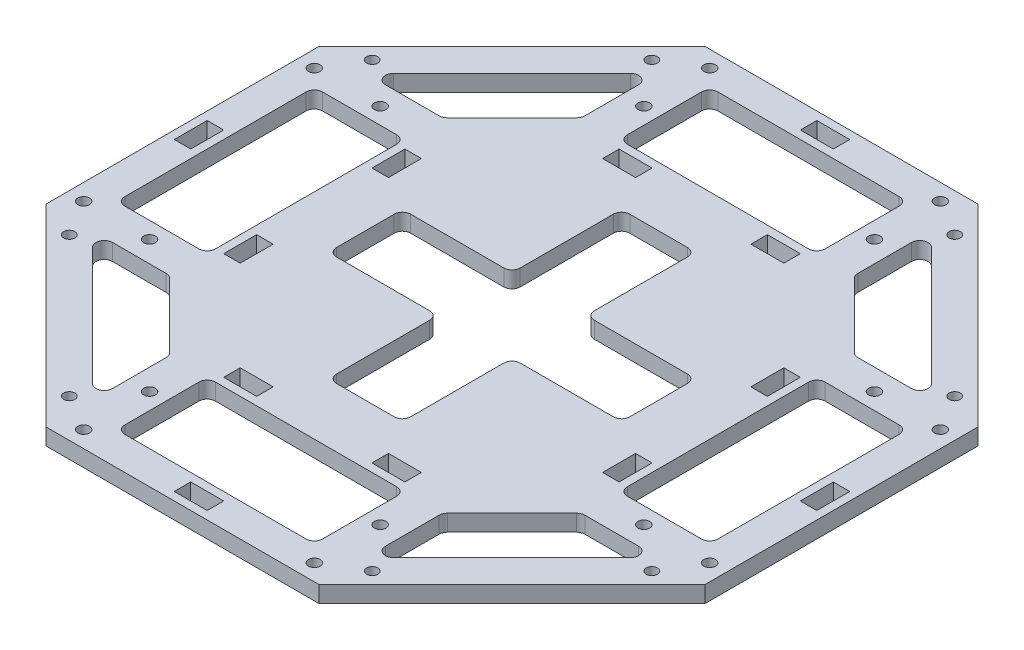
SolidWorks part; units mm, degrees
material "Custom Plastic"
ref_plane "Front Plane" through (0, 0, 0) normal (0, 0, 1) x (1, 0, 0)
ref_plane "Top Plane" through (0, 0, 0) normal (0, 1, 0) x (1, 0, 0)
ref_plane "Right Plane" through (0, 0, 0) normal (1, 0, 0) x (0, 0, -1)
ref_axis "Axis1" through (0, -0.2997, 0) along (0, 1, 0)
sketch "Base sketch" plane through (0, 0, 0) normal (0, 1, 0) x (1, 0, 0)
  line L1 (-127, 52.6051) -> (-127, -52.6051)
  line L2 (-127, -52.6051) -> (-52.6051, -127)
  line L3 (-52.6051, -127) -> (52.6051, -127)
  line L4 (52.6051, -127) -> (127, -52.6051)
  line L5 (127, -52.6051) -> (127, 52.6051)
  line L6 (127, 52.6051) -> (52.6051, 127)
  line L7 (52.6051, 127) -> (-52.6051, 127)
  line L8 (-52.6051, 127) -> (-127, 52.6051)
  circle A0 centre (0, 0) radius 127 construction
  dimension "D1" = 254
extrude "Base" add sketch "Base sketch" along normal blind 6.35
sketch "Sketch3" plane through (0, 6.35, 0) normal (0, 1, 0) x (1, 0, 0)
  line L0 (52.6051, 127) -> (-52.6051, 127) construction
  line L1 (-38.1, 114.3) -> (38.1, 114.3)
  line L2 (-38.1, 114.3) -> (-38.1, 79.375)
  line L4 (-38.1, 79.375) -> (38.1, 79.375)
  line L5 (38.1, 114.3) -> (38.1, 79.375)
  point P6 (0, 79.375)
  dimension "D1" = 76.2
  dimension "D2" = 34.925
  dimension "D3" = 12.7
extrude "Wheel cutout" cut sketch "Sketch3" against normal up to next
fillet "Wheel cutout fillets" radius 3.175 4 edges at (38.1, 3.175, -114.3) (38.1, 3.175, -79.375) (-38.1, 3.175, -79.375) (-38.1, 3.175, -114.3)
pattern_circular "Wheel cutout pattern" count 4 over 360 about axis through (0, -0.2997, 0) along (0, 1, 0) of "Wheel cutout", "Wheel cutout fillets"
sketch "Sketch4" plane through (0, 6.35, 0) normal (0, 1, 0) x (1, 0, 0)
  line L0 (0, 0) -> (0, 127) construction
  line L1 (52.6051, 127) -> (-52.6051, 127) construction
  line L2 (34.925, 120.65) -> (-34.925, 120.65) construction
  line L3 (-34.925, 123.825) -> (-22.225, 123.825) construction
  line L4 (-34.925, 123.825) -> (-34.925, 117.475) construction
  line L5 (-34.925, 117.475) -> (-22.225, 117.475) construction
  line L6 (-22.225, 123.825) -> (-22.225, 117.475) construction
  line L7 (-34.925, 123.825) -> (-22.225, 117.475) construction
  line L8 (-34.925, 117.475) -> (-22.225, 123.825) construction
  line L9 (34.925, 114.3) -> (-34.925, 114.3) construction
  line L10 (34.925, 117.475) -> (22.225, 123.825) construction
  line L11 (34.925, 123.825) -> (22.225, 117.475) construction
  line L12 (22.225, 123.825) -> (22.225, 117.475) construction
  line L13 (34.925, 117.475) -> (22.225, 117.475) construction
  line L14 (34.925, 123.825) -> (34.925, 117.475) construction
  line L15 (34.925, 123.825) -> (22.225, 123.825) construction
  line L16 (-38.1, 96.8375) -> (38.1, 96.8375) construction
  line L17 (-38.1, 111.125) -> (-38.1, 82.55) construction
  line L18 (38.1, 82.55) -> (38.1, 111.125) construction
  line L19 (34.925, 69.85) -> (22.225, 76.2) construction
  line L20 (34.925, 76.2) -> (22.225, 69.85) construction
  line L21 (-34.925, 76.2) -> (-22.225, 69.85) construction
  line L22 (-34.925, 69.85) -> (-22.225, 76.2) construction
  line L23 (34.925, 73.025) -> (-34.925, 73.025) construction
  line L24 (34.925, 69.85) -> (22.225, 69.85)
  line L25 (34.925, 69.85) -> (34.925, 76.2)
  line L26 (34.925, 76.2) -> (22.225, 76.2)
  line L27 (22.225, 69.85) -> (22.225, 76.2)
  line L28 (-22.225, 69.85) -> (-22.225, 76.2)
  line L29 (-34.925, 76.2) -> (-22.225, 76.2)
  line L30 (-34.925, 69.85) -> (-34.925, 76.2)
  line L31 (-34.925, 69.85) -> (-22.225, 69.85)
  line L33 (-6.35, 117.475) -> (6.35, 117.475)
  line L34 (-6.35, 117.475) -> (-6.35, 123.825)
  line L35 (-6.35, 123.825) -> (6.35, 123.825)
  line L36 (6.35, 117.475) -> (6.35, 123.825)
  line L37 (-6.35, 117.475) -> (6.35, 123.825) construction
  line L38 (-6.35, 123.825) -> (6.35, 117.475) construction
  point P5 (-28.575, 120.65)
  point P12 (0, 120.65)
  point P17 (28.575, 120.65)
  point P34 (28.575, 73.025)
  point P35 (-28.575, 73.025)
  point P38 (0, 120.65)
  dimension "D1" = 6.35
  dimension "D2" = 12.7
  dimension "D3" = 69.85
  dimension "D4" = 6.35
  dimension "D5" = 12.7
  dimension "D6" = 6.35
extrude "Support cutouts" cut sketch "Sketch4" against normal up to next
pattern_circular "Support cutout pattern" count 4 over 360 about axis through (0, -0.2997, 0) along (0, 1, 0) of "Support cutouts"
sketch "Sketch9" plane through (0, 6.35, 0) normal (0, 1, 0) x (1, 0, 0)
  line L0 (-109.0395, 52.6051) -> (-52.6051, 109.0395)
  line L1 (-52.6051, 109.0395) -> (-52.6051, 79.375)
  line L2 (-52.6051, 79.375) -> (-79.375, 52.6051)
  line L3 (-79.375, 52.6051) -> (-109.0395, 52.6051)
  line L4 (-52.6051, 127) -> (-127, 52.6051) construction
  line L9 (-79.375, -34.925) -> (-79.375, 34.925) construction
  dimension "D1" = 12.7
extrude "Lightening hole" cut sketch "Sketch9" against normal through all
fillet "Fillet2" radius 3.175 4 edges at (-52.6051, 3.175, -79.375) (-79.375, 3.175, -52.6051) (-109.0395, 3.175, -52.6051) (-52.6051, 3.175, -109.0395)
pattern_circular "Lightening hole pattern" count 4 over 360 about axis through (0, -0.2997, 0) along (0, 1, 0) of "Lightening hole", "Fillet2"
sketch "Sketch22" plane through (0, 6.35, 0) normal (0, 1, 0) x (1, 0, 0)
  line L0 (0, -127) -> (0, 0) construction
  line L1 (-44.45, -95.25) -> (44.45, -95.25) construction
  line L2 (-44.45, -95.25) -> (-44.45, -120.65) construction
  line L3 (-44.45, -120.65) -> (44.45, -120.65) construction
  line L4 (44.45, -95.25) -> (44.45, -120.65) construction
  line L5 (-52.6051, -127) -> (52.6051, -127) construction
  point P9 (0, -95.25)
  dimension "D1" = 6.35
  dimension "D2" = 88.9
  dimension "D3" = 25.4
hole_wizard "Aligner mounting holes" positions "Sketch24" profile "Sketch23" hole size "#8" standard "ANSI Inch" end condition up to next
sketch "Sketch24" plane through (0, 6.35, 0) normal (0, 1, 0) x (1, 0, 0)
  point P0 (-44.45, -95.25)
  point P3 (-44.45, -120.65)
  point P6 (44.45, -120.65)
  point P9 (44.45, -95.25)
sketch "Sketch23" plane through (-44.45, 6.35, 95.25) normal (1, 0, 0) x (0, 0, 1)
  line L0 (0, 0) -> (0, 6.351)
  line L1 (0, 6.351) -> (2.2479, 6.351)
  line L2 (2.2479, 6.351) -> (2.2479, 0)
  line L5 (2.2479, 0) -> (0, 0)
  line L11 (0, -6.35) -> (0, 107.95) construction
  dimension "Thru Hole Dia." = 4.4958
  dimension "Thru Hole Depth" = 6.351
pattern_circular "CirPattern3" count 4 over 360 about axis through (0, -0.2997, 0) along (0, 1, 0) of "Aligner mounting holes"
sketch "Sketch26" plane through (0, 6.35, 0) normal (0, 1, 0) x (1, 0, 0)
  line L0 (-89.8026, 89.8026) -> (0, 0) construction
  line L1 (-52.6051, 127) -> (-127, 52.6051) construction
  line L2 (-112.2532, 58.3717) -> (-58.3717, 112.2532) construction
  line L3 (-58.0252, 103.6194) -> (-103.6194, 58.0252) construction
  dimension "D1" = 6.35
  dimension "D2" = 76.2
hole_wizard "#8 Clearance Hole2" positions "Sketch28" profile "Sketch27" hole size "#8" standard "ANSI Inch" end condition through all
sketch "Sketch28" plane through (0, 6.35, 0) normal (0, 1, 0) x (1, 0, 0)
  point P0 (-58.3717, 112.2532)
  point P7 (-112.2532, 58.3717)
sketch "Sketch27" plane through (-58.3717, 6.35, -112.2532) normal (1, 0, 0) x (0, 0, 1)
  line L0 (0, 0) -> (0, 6.35)
  line L1 (0, 6.35) -> (2.1526, 6.35)
  line L2 (2.1526, 6.35) -> (2.1526, 0)
  line L5 (2.1526, 0) -> (0, 0)
  line L11 (0, -6.35) -> (0, 107.95) construction
  dimension "Thru Hole Dia." = 4.3053
  dimension "Thru Hole Depth" = 6.35
pattern_circular "CirPattern4" count 4 over 360 about axis through (0, -0.2997, 0) along (0, 1, 0) of "#8 Clearance Hole2"
sketch "Sketch30" plane through (0, 6.35, 0) normal (0, 1, 0) x (1, 0, 0)
  line L0 (-14.2875, 56.515) -> (14.2875, 56.515)
  line L1 (14.2875, 56.515) -> (14.2875, 14.2875)
  line L2 (-14.2875, 56.515) -> (-14.2875, 14.2875)
  line L3 (0, 0) -> (0, 79.375) construction
  line L4 (-34.925, 79.375) -> (34.925, 79.375) construction
  line L6 (-14.2875, 14.2875) -> (-56.515, 14.2875)
  line L7 (-56.515, 14.2875) -> (-56.515, -14.2875)
  line L8 (-56.515, -14.2875) -> (-14.2875, -14.2875)
  line L9 (-14.2875, -14.2875) -> (-14.2875, -56.515)
  line L10 (-14.2875, -56.515) -> (14.2875, -56.515)
  line L11 (14.2875, -56.515) -> (14.2875, -14.2875)
  line L12 (14.2875, -14.2875) -> (56.515, -14.2875)
  line L13 (56.515, -14.2875) -> (56.515, 14.2875)
  line L14 (56.515, 14.2875) -> (14.2875, 14.2875)
  line L15 (-79.375, 0) -> (79.375, 0) construction
  line L16 (-79.375, -34.925) -> (-79.375, 34.925) construction
  line L17 (79.375, 34.925) -> (79.375, -34.925) construction
  point P12 (0, 56.515)
  point P24 (56.515, 0)
  dimension "D1" = 22.86
  dimension "D3" = 28.575
extrude "Cut-Extrude2" cut sketch "Sketch30" against normal through all
fillet "Fillet3" radius 3.175 12 edges at (14.2875, 3.175, -56.515) (14.2875, 3.175, -14.2875) (56.515, 3.175, -14.2875) (56.515, 3.175, 14.2875) (14.2875, 3.175, 14.2875) (14.2875, 3.175, 56.515) (-14.2875, 3.175, 56.515) (-14.2875, 3.175, 14.2875) (-56.515, 3.175, 14.2875) (-56.515, 3.175, -14.2875) (-14.2875, 3.175, -56.515) (-14.2875, 3.175, -14.2875)
equation "\"MAT_THICKNESS\"=0.25"
equation "\"D1@Sketch4\"=\"MAT_THICKNESS\""
equation "\"D1@Base\"=\"MAT_THICKNESS\""
equation "\"D6@Sketch4\"=\"MAT_THICKNESS\""
